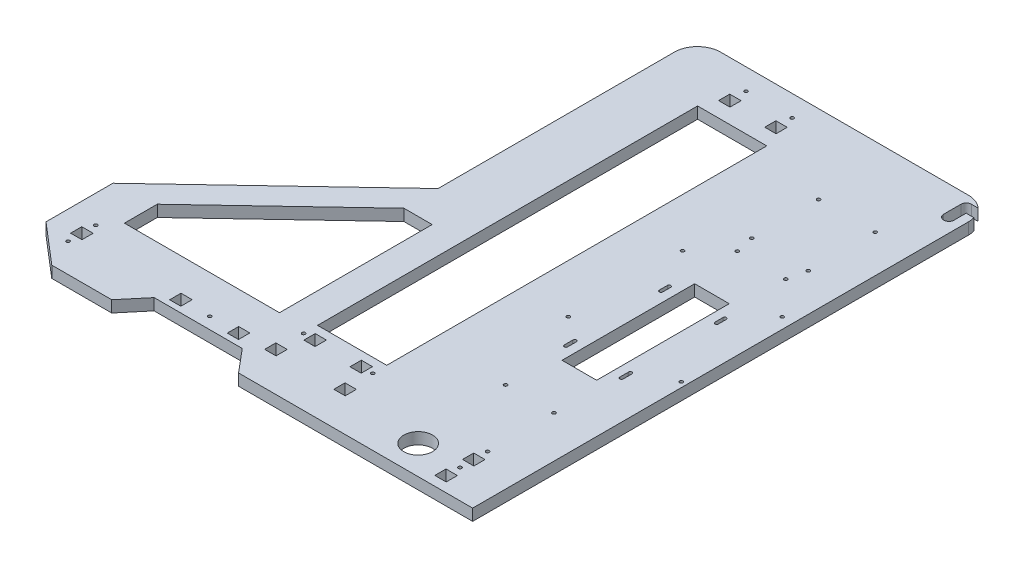
SolidWorks part; units mm, degrees
ref_plane "Front Plane" through (0, 0, 0) normal (0, 0, 1) x (1, 0, 0)
ref_plane "Top Plane" through (0, 0, 0) normal (0, 1, 0) x (1, 0, 0)
ref_plane "Right Plane" through (0, 0, 0) normal (1, 0, 0) x (0, 0, -1)
sketch "Sketch1" plane through (0, 0, 0) normal (0, 1, 0) x (1, 0, 0)
  line L0 (0, 0) -> (-235, 0)
  line L1 (-235, 0) -> (-235, -225)
  line L2 (-235, -225) -> (-380, -362)
  line L3 (-380, -362) -> (-380, -420)
  line L4 (-380, -420) -> (-345, -450)
  line L5 (-345, -450) -> (-293, -450)
  line L6 (-293, -450) -> (-263.6315, -415)
  line L7 (-263.6315, -415) -> (-212.3685, -415)
  line L8 (-212.3685, -415) -> (-183, -450)
  line L9 (-183, -450) -> (0, -450)
  line L10 (0, 0) -> (0, -450)
  line L12 (-293, -450) -> (-183, -450) construction
  dimension "D3" = 235
  dimension "D5" = 58
  dimension "D13" = 190
  dimension "D7" = 35
  dimension "D15" = 52
  dimension "D12" = 30
  dimension "D10" = 35
  dimension "D6" = 380
  dimension "D4" = 450
  dimension "D2" = 50
  dimension "D8" = 50
  dimension "D9" = 110
extrude "Boss-Extrude1" add sketch "Sketch1" along normal blind 10
sketch "Sketch16" plane through (0, 10, 0) normal (0, 1, 0) x (1, 0, 0)
  line L0 (0, -450) -> (20, -450)
  line L1 (20, -450) -> (20, 0)
  line L2 (20, 0) -> (0, 0)
  line L3 (0, 0) -> (0, -450)
  dimension "D1" = 20
  dimension "D2" = 90
extrude "Boss-Extrude2" add sketch "Sketch16" against normal through all
sketch "Sketch2" plane through (0, 10, 0) normal (0, 1, 0) x (1, 0, 0)
  line L0 (-235, -225) -> (-235, -415) construction
  line L1 (-263.6315, -415) -> (-212.3685, -415) construction
  line L2 (-345, -450) -> (-345, -328.931) construction
  line L3 (-235, -225) -> (-380, -362) construction
  line L4 (-345, -358.5097) -> (-235, -254.5787)
  line L5 (-235, -254.5787) -> (-210.5, -254.5787)
  line L6 (-210.5, -254.5787) -> (-210.5, -387)
  line L7 (-210.5, -387) -> (-345, -387)
  line L8 (-345, -387) -> (-345, -358.5097)
  line L9 (0, -450) -> (0, 0) construction
  line L10 (-184.5, -380) -> (-124.5, -380)
  line L11 (-184.5, -380) -> (-184.5, -50.425)
  line L12 (-184.5, -50.425) -> (-124.5, -50.425)
  line L13 (-124.5, -380) -> (-124.5, -50.425)
  line L14 (-124.5, -392.1) -> (-184.5, -392.1) construction
  line L15 (-16, -450) -> (-16, 0) construction
  line L16 (20, 0) -> (-235, 0) construction
  line L17 (-355.9, -440.6571) -> (-355.9, -339.2297) construction
  line L18 (-20.925, -441.85) -> (-11.075, -441.85)
  line L19 (-20.925, -441.85) -> (-20.925, -432.15)
  line L20 (-20.925, -432.15) -> (-11.075, -432.15)
  line L21 (-11.075, -441.85) -> (-11.075, -432.15)
  line L22 (-20.925, -441.85) -> (-11.075, -432.15) construction
  line L23 (-20.925, -432.15) -> (-11.075, -441.85) construction
  line L24 (-20.925, -417.85) -> (-11.075, -417.85)
  line L25 (-20.925, -417.85) -> (-20.925, -408.15)
  line L26 (-20.925, -408.15) -> (-11.075, -408.15)
  line L27 (-11.075, -417.85) -> (-11.075, -408.15)
  line L28 (-20.925, -417.85) -> (-11.075, -408.15) construction
  line L29 (-20.925, -408.15) -> (-11.075, -417.85) construction
  line L30 (-380, -420) -> (-345, -450) construction
  line L32 (-350.975, -408.15) -> (-360.825, -408.15)
  line L33 (-350.975, -408.15) -> (-350.975, -417.85)
  line L34 (-350.975, -417.85) -> (-360.825, -417.85)
  line L35 (-360.825, -408.15) -> (-360.825, -417.85)
  line L36 (-350.975, -408.15) -> (-360.825, -417.85) construction
  line L37 (-350.975, -417.85) -> (-360.825, -408.15) construction
  line L38 (-183, -450) -> (20, -450) construction
  line L39 (-183, -450) -> (20, -450) construction
  line L40 (-173.749, -32.425) -> (-113.749, -32.425) construction
  line L41 (-154.5, -50.425) -> (-154.5, -32.425) construction
  line L42 (-179.425, -27.575) -> (-169.575, -27.575)
  line L43 (-179.425, -27.575) -> (-179.425, -37.275)
  line L44 (-179.425, -37.275) -> (-169.575, -37.275)
  line L45 (-169.575, -27.575) -> (-169.575, -37.275)
  line L46 (-179.425, -27.575) -> (-169.575, -37.275) construction
  line L47 (-179.425, -37.275) -> (-169.575, -27.575) construction
  line L48 (-129.575, -37.275) -> (-139.425, -27.575) construction
  line L49 (-129.575, -27.575) -> (-139.425, -37.275) construction
  line L50 (-139.425, -27.575) -> (-139.425, -37.275)
  line L51 (-129.575, -37.275) -> (-139.425, -37.275)
  line L52 (-129.575, -27.575) -> (-129.575, -37.275)
  line L53 (-129.575, -27.575) -> (-139.425, -27.575)
  line L54 (-174.5, -32.425) -> (-174.5, -18.425) construction
  line L55 (-134.5, -32.425) -> (-134.5, -18.425) construction
  line L56 (-154.5, -380) -> (-154.5, -450) construction
  line L57 (-174.5, -392.1) -> (-134.5, -392.1) construction
  line L58 (-129.65, -397.025) -> (-139.35, -387.175) construction
  line L59 (-179.35, -387.175) -> (-169.65, -387.175)
  line L60 (-179.35, -387.175) -> (-179.35, -397.025)
  line L61 (-179.35, -397.025) -> (-169.65, -397.025)
  line L62 (-169.65, -387.175) -> (-169.65, -397.025)
  line L63 (-179.35, -387.175) -> (-169.65, -397.025) construction
  line L64 (-179.35, -397.025) -> (-169.65, -387.175) construction
  line L65 (-129.65, -387.175) -> (-139.35, -397.025) construction
  line L66 (-139.35, -387.175) -> (-139.35, -397.025)
  line L67 (-129.65, -397.025) -> (-139.35, -397.025)
  line L68 (-129.65, -387.175) -> (-129.65, -397.025)
  line L69 (-129.65, -387.175) -> (-139.35, -387.175)
  line L70 (-119.575, -420.95) -> (-129.425, -411.25) construction
  line L71 (-189.425, -411.25) -> (-179.575, -411.25)
  line L72 (-189.425, -411.25) -> (-189.425, -420.95)
  line L73 (-189.425, -420.95) -> (-179.575, -420.95)
  line L74 (-179.575, -411.25) -> (-179.575, -420.95)
  line L75 (-189.425, -411.25) -> (-179.575, -420.95) construction
  line L76 (-189.425, -420.95) -> (-179.575, -411.25) construction
  line L77 (-119.575, -411.25) -> (-129.425, -420.95) construction
  line L78 (-129.425, -411.25) -> (-129.425, -420.95)
  line L79 (-119.575, -420.95) -> (-129.425, -420.95)
  line L80 (-119.575, -411.25) -> (-119.575, -420.95)
  line L81 (-119.575, -411.25) -> (-129.425, -411.25)
  line L82 (-360.825, -408.15) -> (-11.075, -408.15) construction
  circle A0 centre (-16, -425) radius 1.45
  circle A1 centre (-16, -401) radius 1.45
  circle A2 centre (-355.9, -425) radius 1.45
  circle A3 centre (-355.9, -401) radius 1.45
  circle A4 centre (-174.5, -18.425) radius 1.45
  circle A5 centre (-134.5, -18.425) radius 1.45
  circle A6 centre (-124.5, -392.1) radius 1.45
  circle A7 centre (-184.5, -392.1) radius 1.45
  point P25 (-16, -437)
  point P30 (-16, -413)
  point P44 (-355.9, -413)
  point P61 (-174.5, -32.425)
  point P72 (-134.5, -32.425)
  point P85 (-174.5, -392.1)
  point P94 (-134.5, -392.1)
  point P95 (-184.5, -416.1)
  point P104 (-124.5, -416.1)
  point P105 (-154.5, -392.1)
  dimension "D13" = 2.9
  dimension "D14" = 2.9
  dimension "D23" = 2.9
  dimension "D24" = 2.9
  dimension "D31" = 2.9
  dimension "D37" = 2.9
  dimension "D1" = 21.5
  dimension "D2" = 28
  dimension "D3" = 24.5
  dimension "D4" = 60
  dimension "D7" = 26
  dimension "D8" = 9.7
  dimension "D9" = 9.85
  dimension "D10" = 9.85
  dimension "D11" = 9.7
  dimension "D12" = 24
  dimension "D15" = 24
  dimension "D19" = 9.85
  dimension "D20" = 9.7
  dimension "D26" = 12
  dimension "D27" = 9.85
  dimension "D28" = 9.7
  dimension "D33" = 9.7
  dimension "D38" = 9.85
  dimension "D39" = 9.7
  dimension "D41" = 24
  dimension "D34" = 30
  dimension "D36" = 12.1
  dimension "D30" = 18
  dimension "D29" = 40
  dimension "D17" = 13
  dimension "D32" = 14
  dimension "D35" = 20
  dimension "D16" = 12
  dimension "D21" = 90
  dimension "D25" = 24
  dimension "D5" = 359.75
  dimension "D22" = 349.75
  dimension "D40" = 30
  dimension "D6" = 70
  dimension "D42" = 0
  dimension "D43" = 0
  dimension "D18" = 16
  dimension "D44" = 9.85
extrude "Cut-Extrude1" cut sketch "Sketch2" against normal through all
fillet "Fillet1" radius 20 2 edges at (-235, 5, 0) (20, 5, 0)
sketch "Sketch11" plane through (0, 10, 0) normal (0, 1, 0) x (1, 0, 0)
  line L0 (-124.5, -215.2125) -> (20, -215.2125) construction
  line L1 (20, -450) -> (20, -20) construction
  line L3 (-52.25, -215.2125) -> (-52.25, -450) construction
  line L6 (-124.5, -380) -> (-124.5, -50.425) construction
  line L8 (-183, -450) -> (20, -450) construction
  circle A0 centre (-52.25, -425) radius 12.5
  circle A1 centre (-16, -425) radius 1.45 construction
  dimension "D1" = 25
  dimension "D2" = 0
  dimension "D3" = 0
extrude "WiringHole" cut sketch "Sketch11" against normal through all
sketch "Sketch9" [suppressed] plane through (0, 10, 0) normal (0, 1, 0) x (1, 0, 0)
  line L0 (-52.25, -412.5) -> (-52.25, 0) construction
  line L1 (0, 0) -> (-215, 0) construction
  line L2 (-124.5, -215.2125) -> (20, -215.2125) construction
  line L3 (-124.5, -380) -> (-124.5, -50.425) construction
  line L4 (-4.75, -126.7125) -> (-4.75, -303.7125) construction
  line L6 (-99.75, -126.7125) -> (-4.75, -126.7125) construction
  line L7 (-4.75, -303.7125) -> (-99.75, -303.7125) construction
  line L8 (-99.75, -303.7125) -> (-99.75, -126.7125) construction
  line L9 (20, -450) -> (20, -20) construction
  circle A0 centre (-52.25, -425) radius 12.5 construction
  circle A1 centre (-99.75, -126.7125) radius 1.45
  circle A2 centre (-4.75, -126.7125) radius 1.45
  circle A3 centre (-4.75, -303.7125) radius 1.45
  circle A4 centre (-99.75, -303.7125) radius 1.45
  dimension "D3" = 2.9
  dimension "D4" = 2.9
  dimension "D1" = 95
  dimension "D2" = 177
  dimension "D5" = 47.5
extrude "MountingHoles-PSU" [suppressed] cut sketch "Sketch9" against normal through all
sketch "Sketch10" plane through (0, 10, 0) normal (0, 1, 0) x (1, 0, 0)
  line L0 (-124.5, -215.2125) -> (20, -215.2125) construction
  line L1 (20, -450) -> (20, -20) construction
  line L2 (-52.25, -242.7125) -> (-22.25, -242.7125) construction
  line L3 (-37.25, -210.225) -> (-37.25, 0) construction
  line L4 (-52.25, -215.2125) -> (-52.25, -184.5972) construction
  line L7 (-124.5, -380) -> (-124.5, -50.425) construction
  line L8 (-52.25, -300.2125) -> (-22.25, -300.2125)
  line L9 (-52.25, -300.2125) -> (-52.25, -185.2125)
  line L10 (-52.25, -185.2125) -> (-22.25, -185.2125)
  line L11 (-22.25, -300.2125) -> (-22.25, -185.2125)
  line L12 (-52.25, -300.2125) -> (-22.25, -185.2125) construction
  line L13 (-52.25, -185.2125) -> (-22.25, -300.2125) construction
  line L15 (0, 0) -> (-215, 0) construction
  line L17 (-37.25, -210.225) -> (-37.25, -450) construction
  line L18 (-183, -450) -> (20, -450) construction
  line L19 (-64.75, -215.2125) -> (-39.75, -215.2125) construction
  line L20 (-37.25, -300.2125) -> (-37.25, -185.2125) construction
  dimension "D1" = 30
  dimension "D2" = 115
  dimension "D3" = 0
  dimension "D4" = 0
  dimension "D5" = 0
  dimension "D6" = 27.5
  dimension "D7" = 15
extrude "WiringSlot" cut sketch "Sketch10" against normal through all
sketch "CenterLines" plane through (0, 10, 0) normal (0, 1, 0) x (1, 0, 0)
  line L0 (-37.25, -300.2125) -> (-37.25, -185.2125) construction
  line L1 (-52.25, -300.2125) -> (-22.25, -300.2125) construction
  line L2 (-22.25, -185.2125) -> (-52.25, -185.2125) construction
  line L3 (-52.25, -242.7125) -> (-22.25, -242.7125) construction
  line L4 (-52.25, -185.2125) -> (-52.25, -300.2125) construction
  line L5 (-22.25, -300.2125) -> (-22.25, -185.2125) construction
ref_plane "Plane1" through (-37.25, 0, 0) normal (1, 0, 0) x (0, 0, -1)
sketch "Sketch6" plane through (0, 10, 0) normal (0, 1, 0) x (1, 0, 0)
  line L0 (-37.25, -300.2125) -> (-37.25, -185.2125) construction
  line L1 (-61.35, -242.7125) -> (-13.15, -242.7125) construction
  line L2 (-13.15, -198.2625) -> (-13.15, -280.7625) construction
  line L3 (-52.25, -300.2125) -> (-22.25, -300.2125) construction
  line L4 (-52.25, -242.7125) -> (-22.25, -242.7125) construction
  line L5 (-22.25, -185.2125) -> (-52.25, -185.2125) construction
  line L6 (-13.15, -198.2625) -> (-13.15, -205.2625) construction
  line L7 (-11.7, -198.2625) -> (-11.7, -205.2625)
  line L8 (-14.6, -198.2625) -> (-14.6, -205.2625)
  line L9 (-52.25, -242.7125) -> (-22.25, -242.7125) construction
  line L10 (-52.25, -185.2125) -> (-52.25, -300.2125) construction
  line L11 (-22.25, -300.2125) -> (-22.25, -185.2125) construction
  line L12 (-13.15, -287.7625) -> (-13.15, -280.7625) construction
  line L13 (-14.6, -287.7625) -> (-14.6, -280.7625)
  line L14 (-61.35, -280.1625) -> (-61.35, -205.2625) construction
  line L15 (-13.15, -287.7625) -> (-13.15, -205.2625) construction
  line L16 (-11.7, -287.7625) -> (-11.7, -280.7625)
  arc A2 (-11.7, -198.2625) -> (-14.6, -198.2625) centre (-13.15, -198.2625) ccw
  arc A3 (-14.6, -205.2625) -> (-11.7, -205.2625) centre (-13.15, -205.2625) ccw
  circle A4 centre (-61.35, -280.1625) radius 1.45
  circle A6 centre (-61.35, -205.2625) radius 1.45
  arc A8 (-14.6, -287.7625) -> (-11.7, -287.7625) centre (-13.15, -287.7625) ccw
  arc A9 (-11.7, -280.7625) -> (-14.6, -280.7625) centre (-13.15, -280.7625) ccw
  point P20 (-13.15, -201.7625)
  point P25 (-13.15, -284.2625)
  dimension "D6" = 0
  dimension "D8" = 2.9
  dimension "D12" = 2.9
  dimension "D4" = 1.45
  dimension "D5" = 1.45
  dimension "D11" = 82.5
  dimension "D14" = 74.9
  dimension "D2" = 24.1
  dimension "D3" = 48.2
  dimension "D9" = 7
  dimension "D10" = 7
extrude "MountingHoles-RAMPS" cut sketch "Sketch6" against normal through all
mirror "Mirror1" about plane through (-37.25, 0, 0) normal (1, 0, 0) of "MountingHoles-RAMPS"
sketch "Sketch5" plane through (0, 10, 0) normal (0, 1, 0) x (1, 0, 0)
  line L0 (-22.25, -242.7125) -> (-52.25, -242.7125) construction
  line L3 (-22.25, -300.2125) -> (-22.25, -185.2125) construction
  line L5 (-52.25, -185.2125) -> (-52.25, -300.2125) construction
  line L7 (-16.25, -142.2125) -> (-58.25, -142.2125) construction
  line L8 (-16.25, -343.2125) -> (-58.25, -343.2125) construction
  line L9 (-37.25, -242.7125) -> (-37.25, -142.2125) construction
  line L10 (-37.25, -242.7125) -> (-37.25, -343.2125) construction
  circle A0 centre (-58.25, -142.2125) radius 1.45
  circle A1 centre (-16.25, -142.2125) radius 1.45
  circle A2 centre (-16.25, -343.2125) radius 1.45
  circle A3 centre (-58.25, -343.2125) radius 1.45
  point P17 (-37.25, -142.2125)
  point P22 (-37.25, -343.2125)
  dimension "D2" = 2.9
  dimension "D5" = 2.9
  dimension "D6" = 2.9
  dimension "D7" = 2.9
  dimension "D3" = 201
  dimension "D4" = 100.5
  dimension "D8" = 21
  dimension "D9" = 21
  dimension "D10" = 100.5
extrude "MountingHoles-Melzi" cut sketch "Sketch5" against normal through all
sketch "Sketch13" plane through (0, 0, 0) normal (0, -1, 0) x (-1, 0, 0)
  line L0 (52.25, -215.2125) -> (124.5, -215.2125) construction
  line L1 (124.5, -380) -> (124.5, -50.425) construction
  line L2 (82.25, -264.7275) -> (82.25, -165.6975) construction
  line L3 (37.25, -300.2125) -> (37.25, -185.2125) construction
  line L4 (52.25, -185.2125) -> (52.25, -300.2125) construction
  line L6 (82.25, -264.7275) -> (-15.65, -264.7275) construction
  circle A0 centre (82.25, -165.6975) radius 1.45
  circle A1 centre (82.25, -264.7275) radius 1.45
  circle A2 centre (-10.59, -172.1775) radius 1.45
  circle A3 centre (-15.65, -264.7275) radius 1.45
  point P11 (82.25, -215.2125)
  dimension "D8" = 2.9
  dimension "D6" = 2.9
  dimension "D1" = 2.9
  dimension "D2" = 49.515
  dimension "D3" = 45
  dimension "D4" = 6.48
  dimension "D5" = 92.84
  dimension "D7" = 97.9
extrude "Mountingholes-Smoothieboard" cut sketch "Sketch13" against normal through all
mirror "Flipped" [suppressed] about plane through (-37.25, 0, 0) normal (1, 0, 0)
sketch "Sketch21" plane through (0, 10, 0) normal (0, 1, 0) x (1, 0, 0)
  line L0 (-37.25, -185.2125) -> (-37.25, 0) construction
  line L1 (-22.25, -185.2125) -> (-52.25, -185.2125) construction
  line L2 (0, 0) -> (-215, 0) construction
  line L3 (-37.25, -97.2125) -> (-23.3697, -97.2125) construction
  circle A0 centre (-12.75, -68.2125) radius 1.45
  circle A1 centre (-61.75, -68.2125) radius 1.45
  circle A2 centre (-61.75, -126.2125) radius 1.45
  circle A3 centre (-12.75, -126.2125) radius 1.45
  circle A4 centre (-16.25, -142.2125) radius 1.45 construction
  dimension "D1" = 2.9
  dimension "D2" = 24.5
  dimension "D3" = 29
  dimension "D4" = 45
extrude "Pi" cut sketch "Sketch21" against normal through all
sketch "Sketch17" plane through (0, 10, 0) normal (0, 1, 0) x (1, 0, 0)
  line L0 (0, 0) -> (20, 0) construction
  line L1 (20, -23.6361) -> (20, 0) construction
  line L2 (20, -450) -> (20, -20) construction
  line L3 (20, -10) -> (8, -10) construction
  line L4 (20, -14.5) -> (8, -14.5)
  line L5 (20, -5.5) -> (8, -5.5)
  arc A0 (20, -14.5) -> (20, -5.5) centre (20, -10) ccw
  arc A1 (8, -5.5) -> (8, -14.5) centre (8, -10) ccw
  point P8 (14, -10)
  dimension "D1" = 9
  dimension "D2" = 12
  dimension "D3" = 10
extrude "Cut-Extrude3" cut sketch "Sketch17" against normal through all
sketch "Sketch18" plane through (0, 10, 0) normal (0, 1, 0) x (1, 0, 0)
  line L0 (8, -5.5) -> (8, -14.5) construction
  line L1 (3.5, -10) -> (8, -10) construction
  line L2 (8, -10) -> (8, -25) construction
  line L3 (12.5, -10) -> (12.5, -25)
  line L4 (3.5, -10) -> (3.5, -25)
  arc A0 (8, -5.5) -> (8, -14.5) centre (8, -10) ccw construction
  arc A1 (12.5, -10) -> (3.5, -10) centre (8, -10) ccw
  arc A2 (3.5, -25) -> (12.5, -25) centre (8, -25) ccw
  point P10 (8, -17.5)
  dimension "D1" = 9
  dimension "D2" = 0
  dimension "D3" = 15
extrude "Cut-Extrude4" cut sketch "Sketch18" against normal through all
sketch "Sketch19" plane through (0, 10, 0) normal (0, 1, 0) x (1, 0, 0)
  line L0 (-2, -25) -> (18, -25) construction
  line L1 (8, -25) -> (8, -5.5) construction
  circle A0 centre (18, -25) radius 1.45
  arc A1 (8, -5.5) -> (3.5, -10) centre (8, -10) ccw construction
  circle A2 centre (-2, -25) radius 1.45
  dimension "D2" = 2.9
extrude "Cut-Extrude5" [suppressed] cut sketch "Sketch19" against normal through all
sketch "Sketch22" plane through (0, 10, 0) normal (0, 1, 0) x (1, 0, 0)
  line L0 (-276.218, -430) -> (-199.782, -430)
  line L1 (-293, -450) -> (-263.6315, -415) construction
  line L2 (-212.3685, -415) -> (-183, -450) construction
  line L3 (-199.782, -430) -> (-212.3685, -415)
  line L4 (-212.3685, -415) -> (-263.6315, -415)
  line L5 (-263.6315, -415) -> (-276.218, -430)
  dimension "D1" = 15
extrude "Boss-Extrude3" add sketch "Sketch22" against normal through all
sketch "Sketch23" plane through (0, 10, 0) normal (0, 1, 0) x (1, 0, 0)
  line L0 (-238, -430) -> (-238, -387) construction
  line L1 (-276.218, -430) -> (-199.782, -430) construction
  line L2 (-345, -387) -> (-210.5, -387) construction
  line L3 (-213, -420) -> (-263, -420) construction
  line L4 (-179.35, -387.175) -> (-179.35, -397.025) construction
  line L5 (-267.85, -415.075) -> (-258.15, -415.075)
  line L6 (-267.85, -415.075) -> (-267.85, -424.925)
  line L7 (-267.85, -424.925) -> (-258.15, -424.925)
  line L8 (-258.15, -415.075) -> (-258.15, -424.925)
  line L9 (-267.85, -415.075) -> (-258.15, -424.925) construction
  line L10 (-267.85, -424.925) -> (-258.15, -415.075) construction
  line L11 (-208.15, -424.925) -> (-217.85, -415.075) construction
  line L12 (-208.15, -415.075) -> (-217.85, -424.925) construction
  line L13 (-217.85, -415.075) -> (-217.85, -424.925)
  line L14 (-208.15, -424.925) -> (-217.85, -424.925)
  line L15 (-208.15, -415.075) -> (-208.15, -424.925)
  line L16 (-208.15, -415.075) -> (-217.85, -415.075)
  circle A0 centre (-238, -420) radius 1.45
  point P19 (-238, -420)
  dimension "D4" = 2.9
  dimension "D1" = 9.7
  dimension "D3" = 10
extrude "Cut-Extrude6" cut sketch "Sketch23" against normal through all
equation "\"Y-ROD-SPACING\"=75"
equation "\"Y-BED-OFFSET\"=2"
equation "\"Y-BED-ROD-INSET\"=3.5"
equation "\"T-SLOT-NUT-FILLET-RADIUS\"=0.5"
equation "\"T-SLOT-SCREW-SHAFT-RADIUS\"=1.55"
equation "\"T-SLOT-SCREW-SHAFT-CUTOUT-LENGTH\"=11"
equation "\"T-SLOT-NUT-DEPTH\"=3.5"
equation "\"T-SLOT-NUT-WIDTH\"=2.85"
equation "\"T-SLOT-NUT-END-DISTANCE\"=8"
equation "\"ACRYLIC-TAB-CUTOUT-SIZE\"=\"ACRYLIC-THICKNESS\"+\"ACRYLIC-TAB-TOLERANCE\"*2"
equation "\"ACRYLIC-TAB-WIDTH\"=\"ACRYLIC-THICKNESS\""
equation "\"ACRYLIC-M3-HOLE\"=2.9"
equation "\"SMOOTHROD-CAP-SCREW-DISTANCE\"=20"
equation "\"FRAME-WIDTH-INNER\"=370"
equation "\"D24@Sketch2\"=\"ACRYLIC-M3-HOLE\""
equation "\"D23@Sketch2\"=\"ACRYLIC-M3-HOLE\""
equation "\"D19@Sketch2\"=\"ACRYLIC-THICKNESS\"-\"KERF\"*2"
equation "\"D20@Sketch2\"=\"ACRYLIC-TAB-WIDTH\"-\"KERF\"*4"
equation "\"D37@Sketch2\"=\"ACRYLIC-M3-HOLE\""
equation "\"D33@Sketch2\"=\"ACRYLIC-TAB-WIDTH\"-\"KERF\"*4"
equation "\"D38@Sketch2\"=\"ACRYLIC-THICKNESS\"-\"KERF\"*2"
equation "\"D39@Sketch2\"=\"ACRYLIC-TAB-WIDTH\"-\"KERF\"*4"
equation "\"D13@Sketch2\"=\"ACRYLIC-M3-HOLE\""
equation "\"D14@Sketch2\"=\"ACRYLIC-M3-HOLE\""
equation "\"D8@Sketch2\"=\"ACRYLIC-TAB-WIDTH\"-\"KERF\"*4"
equation "\"D9@Sketch2\"=\"ACRYLIC-THICKNESS\"-\"KERF\"*2"
equation "\"D10@Sketch2\"=\"ACRYLIC-THICKNESS\"-\"KERF\"*2"
equation "\"D11@Sketch2\"=\"ACRYLIC-TAB-WIDTH\"-\"KERF\"*4"
equation "\"D31@Sketch2\"=\"ACRYLIC-M3-HOLE\""
equation "\"D27@Sketch2\"=\"ACRYLIC-THICKNESS\"-\"KERF\"*2"
equation "\"D28@Sketch2\"=\"ACRYLIC-TAB-WIDTH\"-\"KERF\"*4"
equation "\"NEMA17-HOLE-SPACING\"=31"
equation "\"NEMA17-CENTRAL-CUTOUT\"=22.5"
equation "\"Z-BRACKET-REACH\"=57"
equation "\"TOP-BRACKET-SPACING\"=40"
equation "\"D29@Sketch2\"=\"TOP-BRACKET-SPACING\""
equation "\"ACRYLIC-THICKNESS\"=10"
equation "\"SMOOTHROD-Z-LENGTH\"=350"
equation "\"D5@Sketch2\"=\"SMOOTHROD-Z-LENGTH\"-\"SMOOTHROD-TIGHTENING-HEADROOM\"+10"
equation "\"SMOOTHROD-X-LENGTH\"=350"
equation "\"SMOOTHROD-Y-LENGTH\"=350"
equation "\"D22@Sketch2\"=\"SMOOTHROD-Y-LENGTH\"-\"SMOOTHROD-TIGHTENING-HEADROOM\""
equation "\"SMOOTHROD-TIGHTENING-HEADROOM\"=.25"
equation "\"X-ROD-SPACING\"=45"
equation "\"Z-ROD-SPACING\"=17.5"
equation "\"LEADSCREW-Z-LENGTH\"=300"
equation "\"SCREW-HEAD-RADIUS\"=6"
equation "\"PRINTED-X-SMOOTHROD-DIAMETER\"=8.8"
equation "\"PRINTED-X-SMOOTHROD-CUTOUT\"=10"
equation "\"PRINTED-X-BASE-HEIGHT\"=10"
equation "\"PRINTED-LM8UU-CUTOUT-SIZE\"=15.5"
equation "\"PRINTED-LM8UU-CUTOUT-LENGTH\"=24.5"
equation "\"PRINTED-X-IDLER-HEIGHT\"=16"
equation "\"PSU-MOUNTING-WIDTH\"=95"
equation "\"PSU-MOUNTING-HEIGHT\"=177"
equation "\"D1@Sketch9\"=\"PSU-MOUNTING-WIDTH\""
equation "\"D3@Sketch9\"=\"ACRYLIC-M3-HOLE\""
equation "\"D1@Boss-Extrude1\"=\"ACRYLIC-THICKNESS\""
equation "\"D6@Sketch1\"=\"SMOOTHROD-Y-LENGTH\"+30"
equation "\"D4@Sketch9\"=\"ACRYLIC-M3-HOLE\""
equation "\"D2@Sketch9\"=\"PSU-MOUNTING-HEIGHT\""
equation "\"D5@Sketch9\"=\"PSU-MOUNTING-WIDTH\"/2"
equation "\"D4@Sketch1\"=\"SMOOTHROD-Z-LENGTH\"+100"
equation "\"D8@Sketch6\"=\"ACRYLIC-M3-HOLE\""
equation "\"D12@Sketch6\"=\"ACRYLIC-M3-HOLE\""
equation "\"D2@Sketch5\"=\"ACRYLIC-M3-HOLE\""
equation "\"D5@Sketch5\"=\"ACRYLIC-M3-HOLE\""
equation "\"D6@Sketch5\"=\"ACRYLIC-M3-HOLE\""
equation "\"D7@Sketch5\"=\"ACRYLIC-M3-HOLE\""
equation "\"D1@Sketch13\"=\"ACRYLIC-M3-HOLE\""
equation "\"D6@Sketch13\"=\"ACRYLIC-M3-HOLE\""
equation "\"D8@Sketch13\"=\"ACRYLIC-M3-HOLE\""
equation "\"D4@Sketch6\"=\"ACRYLIC-M3-HOLE\"/2"
equation "\"D5@Sketch6\"=\"ACRYLIC-M3-HOLE\"/2"
equation "\"Y-BED-SCREW-SPACING\"=209"
equation "\"Y-BED-SCREW-CUTOUT-SLOT-HEIGHT\"=2.5"
equation "\"ACRYLIC-THICKNESS2\"=4.5"
equation "\"ACRYLIC-TAB-TOLERANCE\"=-.05"
equation "\"Z-ROD-INSET\"=13.5"
equation "\"SCREW-LENGTH-FRAME\"=\"ACRYLIC-THICKNESS\" + 10"
equation "\"SCREW-LENGTH-MOTOR\"=\"ACRYLIC-THICKNESS\" + 5"
equation "\"SCREW-LENGTH-EXTRUDER\"=28"
equation "\"Y-BELT-TO-ROD-DISTANCE\"=20"
equation "\"SPOOL-HOLDER-ROD-SPACING\"=150"
equation "\"ACRYLIC-X-CARRIAGE-WIDTH\"=55"
equation "\"ACRYLIC-X-CARRIAGE-HEIGHT\"=75"
equation "\"ACRYLIC-X-CARRIAGE-LM8UU-CUTOUT-WIDTH\"=24.25"
equation "\"ACRYLIC-X-CARRIAGE-SCREW-SPACING-X\"=15"
equation "\"ACRYLIC-X-CARRIAGE-SCREW-SPACING-Y\"=33"
equation "\"ACRYLIC-X-CARRIAGE-CENTER-TAB-SPACING\"=14"
equation "\"ACRYLIC-X-CARRIAGE-EXTRUDER-OFFSET\"=26"
equation "\"ACRYLIC-X-CARRIAGE-EXTRUDER-ANGLE\"=90"
equation "\"ACRYLIC-X-CARRIAGE-EXTRUDER-SHELF-DEPTH\"=\"ACRYLIC-X-CARRIAGE-EXTRUDER-OFFSET\" + 28"
equation "\"ACRYLIC-X-CARRIAGE-EXTRUDER-BRACE-SPACING\"=23"
equation "\"ACRYLIC-X-CARRIAGE-EXTRUDER-BRACE-TAB-OFFSET\"=20"
equation "\"ACRYLIC-X-CARRIAGE-EXTRUDER-BRACE-HEIGHT\"=35"
equation "\"ACRYLIC-X-CARRIAGE-EXTRUDER-BRACE-SCREW-SPACING\"=22"
equation "\"D1@Sketch19\"=\"SMOOTHROD-CAP-SCREW-DISTANCE\"/2"
equation "\"D2@Sketch19\"=\"ACRYLIC-M3-HOLE\""
equation "\"D1@Sketch21\"=\"ACRYLIC-M3-HOLE\""
equation "\"KERF\"=0.075"
equation "\"PRINTED-M3-HOLE\"=3.5"
equation "\"PRINTED-M3-NUT-AF\"=6.25"
equation "\"ACRYLIC-X-CARRIAGE-LM8UU-CUTOUT-HEIGHT\"=11.0"
equation "\"ACRYLIC-X-CARRIAGE-DUAL-WIDTH-MULTIPLIER\"=1.65"
equation "\"ACRYLIC-X-CARRIAGE-DUAL-HOTEND-SPACING\"=42"
equation "\"ACRYLIC-X-CARRIAGE-DUAL-WIDTH\"=75"
equation "\"ACRYLIC-X-CARRIAGE-DUAL-FAN-OFFSET\"=52"
equation "\"ACRYLIC-X-CARRIAGE-DUAL-FAN-HEIGHT\"=20"
equation "\"ACRYLIC-X-CARRIAGE-DUAL-HOTEND-SEPARATION\"=36"
equation "\"ACRYLIC-X-CARRIAGE-DUAL-MOUNT-PLATE-DEPTH\"=75"
equation "\"ACRYLIC-X-CARRIAGE-DUAL-MOUNT-BRACE-WIDTH\"=33"
equation "\"ACRYLIC-X-CARRIAGE-DUAL-MOUNT-SCREW-WIDTH\"=40"
equation "\"BLOWER-FAN-WIDTH\"=15"
equation "\"D44@Sketch2\"=\"ACRYLIC-THICKNESS\"-\"KERF\"*2"
equation "\"D1@Sketch23\"=10-\"KERF\"*4"
equation "\"D4@Sketch23\"=\"ACRYLIC-M3-HOLE\""
